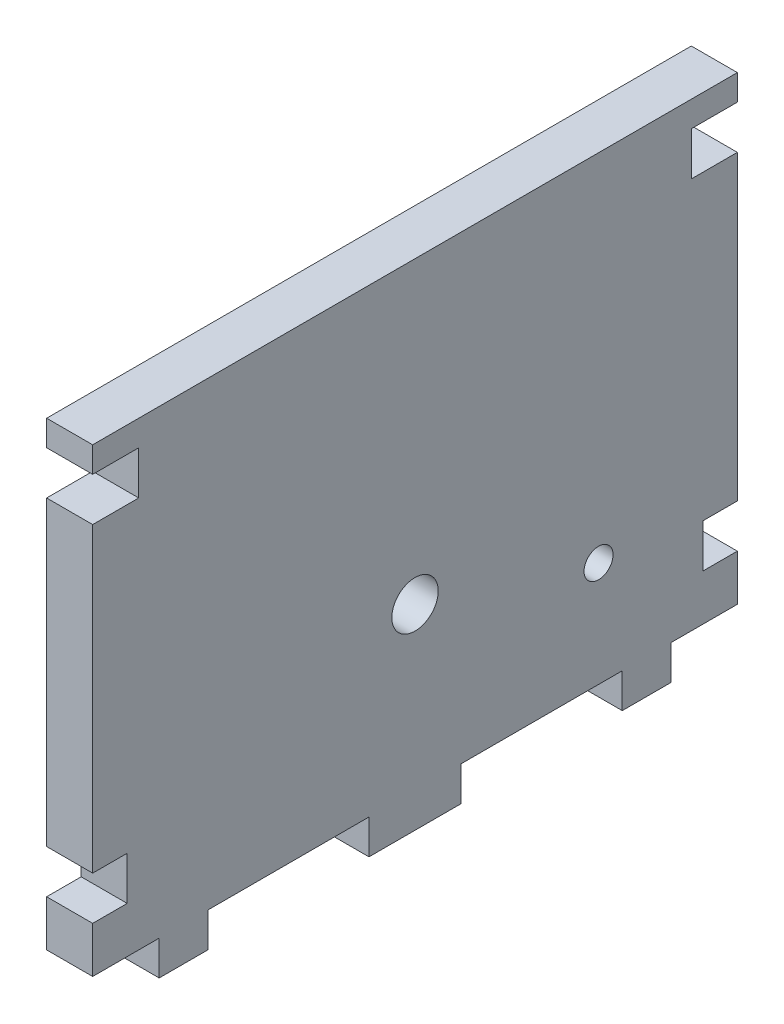
SolidWorks part; units mm, degrees
ref_plane "Front Plane" through (0, 0, 0) normal (0, 0, 1) x (1, 0, 0)
ref_plane "Top Plane" through (0, 0, 0) normal (0, 1, 0) x (1, 0, 0)
ref_plane "Right Plane" through (0, 0, 0) normal (1, 0, 0) x (0, 0, -1)
sketch "Sketch1" plane through (0, 0, 0) normal (1, 0, 0) x (0, 0, -1)
  line L0 (28.575, -26.9875) -> (28.575, -22.225)
  line L1 (44.45, -22.225) -> (-44.45, -22.225)
  line L2 (44.45, -22.225) -> (44.45, 22.225)
  line L3 (44.45, 22.225) -> (-44.45, 22.225)
  line L4 (-44.45, -22.225) -> (-44.45, 22.225)
  line L5 (0, 22.225) -> (0, -22.225) construction
  line L6 (44.45, 0) -> (-44.45, 0) construction
  line L7 (6.35, -26.9875) -> (-6.35, -26.9875)
  line L8 (6.35, -26.9875) -> (6.35, -22.225)
  line L9 (6.35, -22.225) -> (-6.35, -22.225)
  line L10 (-6.35, -26.9875) -> (-6.35, -22.225)
  line L11 (0, -22.225) -> (0, -26.9875) construction
  line L12 (6.35, -24.6062) -> (-6.35, -24.6062) construction
  line L13 (-28.575, -26.9875) -> (-35.2806, -26.9875)
  line L14 (-28.575, -26.9875) -> (-28.575, -22.225)
  line L15 (-28.575, -22.225) -> (-35.2806, -22.225)
  line L16 (-35.2806, -26.9875) -> (-35.2806, -22.225)
  line L17 (-31.9278, -22.225) -> (-31.9278, -26.9875) construction
  line L18 (-28.575, -24.6062) -> (-35.2806, -24.6062) construction
  line L19 (28.575, -22.225) -> (35.2806, -22.225)
  line L20 (35.2806, -26.9875) -> (35.2806, -22.225)
  line L21 (28.575, -26.9875) -> (35.2806, -26.9875)
  line L22 (-44.45, 41.275) -> (44.45, 41.275)
  line L23 (39.6875, -15.875) -> (39.6875, -9.8806)
  line L24 (39.6875, -9.8806) -> (44.45, -9.8806)
  line L25 (-44.45, -9.8806) -> (-39.6875, -9.8806)
  line L26 (-39.6875, -9.8806) -> (-39.6875, -15.875)
  line L27 (-44.45, 41.275) -> (-44.45, 22.225)
  line L28 (-44.45, 22.225) -> (-43.6191, 22.0477)
  line L29 (44.45, 41.275) -> (44.45, 22.225)
  line L30 (39.6875, -15.875) -> (44.45, -15.875)
  line L31 (-39.6875, -15.875) -> (-44.45, -15.875)
  line L33 (44.45, 37.7444) -> (38.1, 37.7444)
  line L34 (44.45, 37.7444) -> (44.45, 31.75)
  line L35 (44.45, 31.75) -> (38.1, 31.75)
  line L36 (38.1, 37.7444) -> (38.1, 31.75)
  line L37 (-44.45, 37.7444) -> (-38.1, 37.7444)
  line L38 (-44.45, 37.7444) -> (-44.45, 31.75)
  line L39 (-44.45, 31.75) -> (-38.1, 31.75)
  line L40 (-38.1, 37.7444) -> (-38.1, 31.75)
  circle A0 centre (0, 0) radius 3.2004
  circle A1 centre (25.3091, -7.7249) radius 2
  point P0 (0, 0)
  point P4 (0, -24.6062)
  point P8 (-31.9278, -24.6062)
  dimension "D7" = 6.4008
  dimension "D8" = 4
  dimension "D1" = 4.7625
  dimension "D2" = 6.7056
  dimension "D3" = 12.7
  dimension "D4" = 57.15
  dimension "D5" = 44.45
  dimension "D6" = 88.9
  dimension "D9" = 25.3091
  dimension "D10" = 7.7249
  dimension "D11" = 63.5
  dimension "D12" = 5.9944
  dimension "D13" = 4.7625
  dimension "D14" = 6.35
  dimension "D15" = 9.525
  dimension "D16" = 5.9944
  dimension "D17" = 6.35
extrude "Boss-Extrude1" add sketch "Sketch1" along normal blind 6.35 contours L4 L1 L2 L3 A1 A0 | L0 L21 L20 L1 | L10 L7 L8 L1 | L16 L13 L14 L1 | L29 L22 L27 L3 region at (0, -24.6062, -31.9278) region at (0, -21.2311, -17.4625) region at (0, -24.6062, 0) region at (0, -24.6062, 31.9278) region at (0, 31.6089, 0)
sketch "Sketch2" plane through (6.35, 0, 0) normal (1, 0, 0) x (0, 0, -1)
  line L0 (-44.45, -22.225) -> (-44.45, -15.875) construction
  line L1 (-38.1, -9.525) -> (-44.45, -9.525)
  line L2 (-38.1, -9.525) -> (-38.1, 3.175)
  line L3 (-38.1, 3.175) -> (-44.45, 3.175)
  line L4 (-44.45, -9.525) -> (-44.45, 3.175)
  line L5 (-41.275, 3.175) -> (-41.275, -9.525) construction
  line L6 (-38.1, -3.175) -> (-44.45, -3.175) construction
  line L7 (-35.2806, -22.225) -> (-44.45, -22.225) construction
  line L8 (0, 0) -> (0, 19.6541) construction
  line L9 (38.1, -9.525) -> (44.45, -9.525)
  line L10 (44.45, -9.525) -> (44.45, 3.175)
  line L11 (38.1, 3.175) -> (44.45, 3.175)
  line L12 (38.1, -9.525) -> (38.1, 3.175)
  point P0 (-41.275, -3.175)
  dimension "D1" = 6.35
  dimension "D2" = 12.7
  dimension "D3" = 12.7
extrude "Cut-Extrude1" [suppressed] cut sketch "Sketch2" against normal blind 6.35
fillet "Fillet1" [suppressed] radius 1.27
equation "\"D2@Sketch1\"=.25+.014"
equation "\"D3@Sketch1\"=.5"
